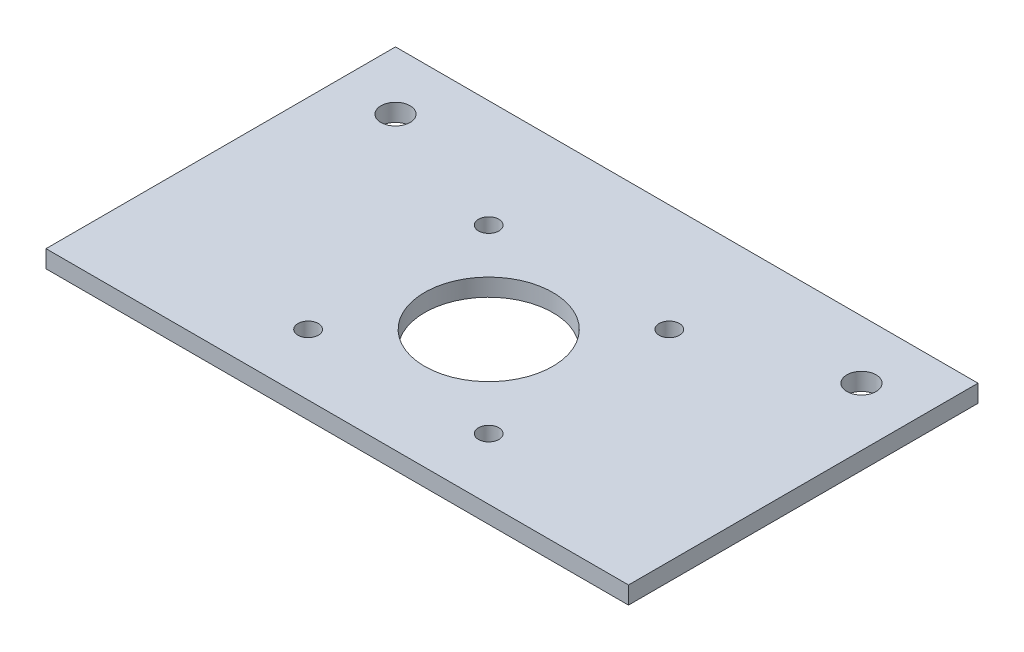
SolidWorks part; units mm, degrees
note: The reader was unsure of these and kept them because the rebuilt part matched: thickness of "Base-Flange1", "Sheet-Metal1", "Sheet-Metal2".
material "Wrought Stainless Steel"
ref_plane "Front Plane" through (0, 0, 0) normal (0, 0, 1) x (1, 0, 0)
ref_plane "Top Plane" through (0, 0, 0) normal (0, 1, 0) x (1, 0, 0)
ref_plane "Right Plane" through (0, 0, 0) normal (1, 0, 0) x (0, 0, -1)
sketch "Sketch1" plane through (0, 0, 0) normal (0, 1, 0) x (1, 0, 0)
  line L1 (-50, -30) -> (50, -30)
  line L2 (-50, -30) -> (-50, 30)
  line L3 (-50, 30) -> (50, 30)
  line L4 (50, -30) -> (50, 30)
  line L5 (-50, -30) -> (50, 30) construction
  line L6 (-50, 30) -> (50, -30) construction
  point P0 (0, 0)
  dimension "D1" = 100
  dimension "D2" = 60
base flange "Base-Flange1" sketch "Sketch1" thickness 3 reverse thickness direction no parameters "D1"=1
sketch "Sketch6" plane through (0, 0, 0) normal (0, 1, 0) x (1, 0, 0)
  line L0 (0, -1000) -> (0, 49000) construction
  line L1 (-1040, 20) -> (48960, 20) construction
  line L6 (30, 10) -> (50, 10) construction
  line L7 (30, 10) -> (30, 30) construction
  line L8 (30, 30) -> (50, 30) construction
  line L9 (50, 10) -> (50, 30) construction
  line L10 (30, 10) -> (50, 30) construction
  line L11 (30, 30) -> (50, 10) construction
  line L12 (-7.4521, -4) -> (7.4521, -4) construction
  circle A0 centre (40, 20) radius 2.5
  circle A1 centre (-40, 20) radius 2.5
  circle A2 centre (0, -4) radius 11
  circle A3 centre (15.5, 11.5) radius 1.75
  circle A4 centre (15.5, -19.5) radius 1.75
  circle A5 centre (-15.5, -19.5) radius 1.75
  circle A6 centre (-15.5, 11.5) radius 1.75
  point P1 (40, 20)
  point P19 (0, -4)
  dimension "D3" = 5
  dimension "D5" = 22
  dimension "D7" = 15.5
  dimension "D8" = 3.5
  dimension "D1" = 20
  dimension "D2" = 20
  dimension "D4" = 24
  dimension "D6" = 15.5
extrude "Cut-Extrude1" cut sketch "Sketch6" against normal blind 10
sketch "Bend-Lines1" [suppressed] plane through (0, 0, 0) normal (0, 1, 0) x (1, 0, 0)
sketch "Bounding-Box1" [suppressed] plane through (0, 0, 0) normal (0, 1, 0) x (1, 0, 0)
sheet metal parameters "Sheet-Metal1" thickness 3 parameters "D1"=1, "D7"=5
flat pattern "Flat-Pattern1" [suppressed]
sketch "Bend-Lines2" plane through (0, 0, 0) normal (0, 1, 0) x (1, 0, 0)
sketch3d "Bounding-Box2" [suppressed]
  line L0 (-50, 35, 0) -> (50, 35, 0) construction
  line L1 (-50, -35, 0) -> (50, -35, 0) construction
  line L2 (-50, 35, 0) -> (-50, -35, 0) construction
  line L3 (50, 35, 0) -> (50, -35, 0) construction
sheet metal parameters "Sheet-Metal2" thickness 3 parameters "D1"=1, "D7"=5
flat pattern "Flat-Pattern1"
sketch "Bend-Lines2" plane through (0, 0, 0) normal (0, 1, 0) x (1, 0, 0)
sketch3d "Bounding-Box2" [suppressed]
  line L0 (50, 30, 0) -> (-50, 30, 0) construction
  line L1 (50, -30, 0) -> (-50, -30, 0) construction
  line L2 (50, 30, 0) -> (50, -30, 0) construction
  line L3 (-50, 30, 0) -> (-50, -30, 0) construction
